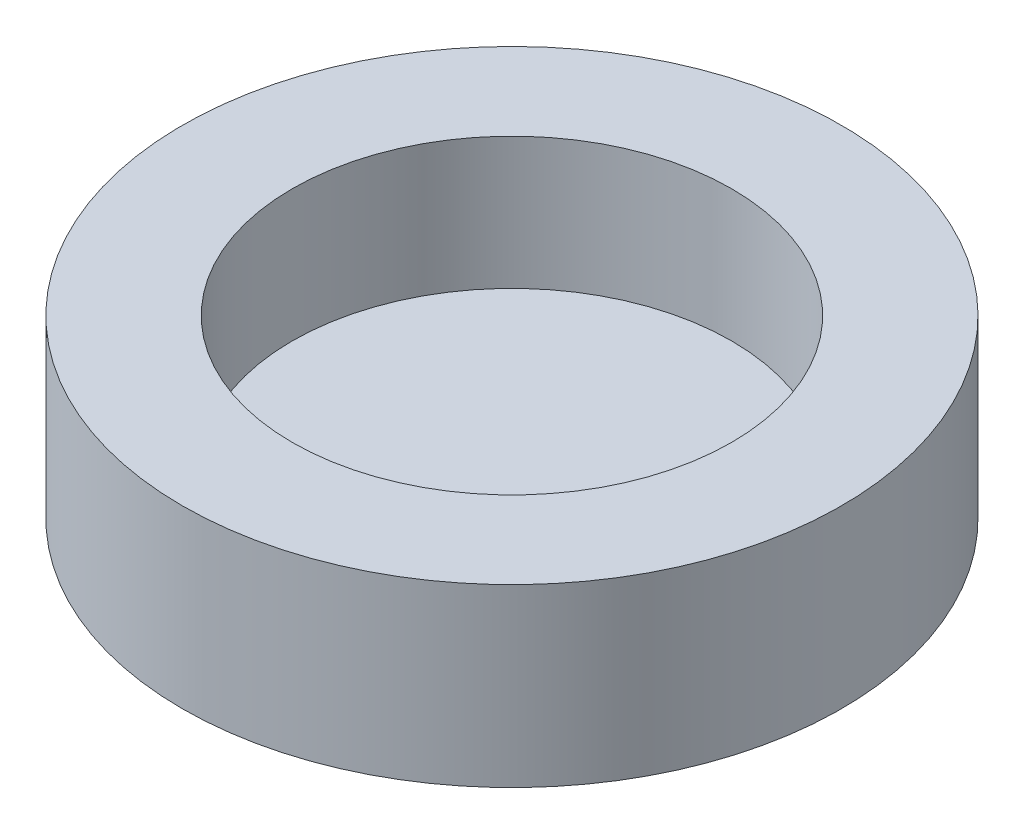
SolidWorks part; units mm, degrees
ref_plane "Front Plane" through (0, 0, 0) normal (0, 0, 1) x (1, 0, 0)
ref_plane "Top Plane" through (0, 0, 0) normal (0, 1, 0) x (1, 0, 0)
ref_plane "Right Plane" through (0, 0, 0) normal (1, 0, 0) x (0, 0, -1)
sketch "Sketch1" plane through (0, 0, 0) normal (0, 1, 0) x (1, 0, 0)
  circle A0 centre (0, 0) radius 7.5
  dimension "D1" = 15
extrude "Boss-Extrude1" add sketch "Sketch1" along normal blind 4
sketch "Sketch2" plane through (0, 4, 0) normal (0, 1, 0) x (1, 0, 0)
  circle A0 centre (0, 0) radius 5
  dimension "D1" = 10
extrude "Cut-Extrude1" cut sketch "Sketch2" against normal blind 3
